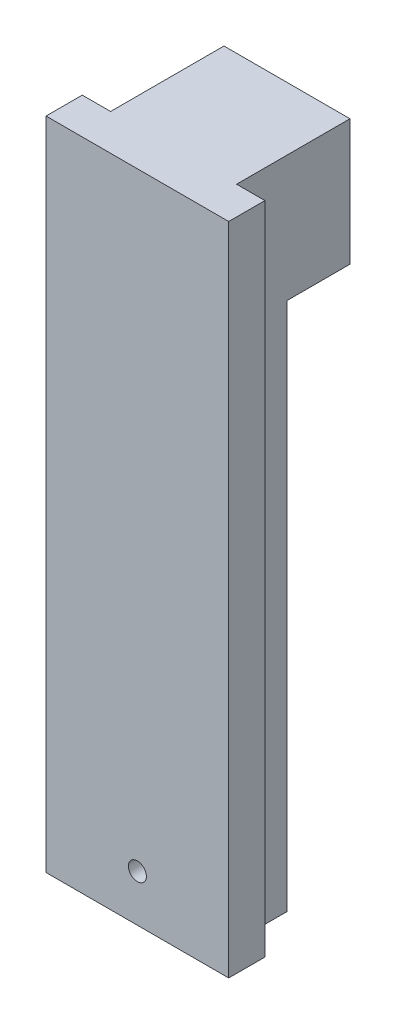
SolidWorks part; units mm, degrees
ref_plane "Płaszczyzna przednia" through (0, 0, 0) normal (0, 0, 1) x (1, 0, 0)
ref_plane "Płaszczyzna górna" through (0, 0, 0) normal (0, 1, 0) x (1, 0, 0)
ref_plane "Płaszczyzna prawa" through (0, 0, 0) normal (1, 0, 0) x (0, 0, -1)
sketch "Szkic1" plane through (0, 0, 0) normal (0, 1, 0) x (1, 0, 0)
  line L0 (0, -6) -> (0, 0) construction
  line L1 (0, 13.75) -> (0, 0) construction
  line L7 (-14.5, 0) -> (14.5, 0)
  line L8 (19, 5.75) -> (10, 5.75) construction
  line L10 (14.5, 0) -> (14.5, 5.75)
  line L11 (14.5, 5.75) -> (10, 5.75)
  line L12 (10, 5.75) -> (10, 13.75)
  line L13 (10, 13.75) -> (-10, 13.75)
  line L14 (-10, 13.75) -> (-10, 5.75)
  line L15 (-10, 5.75) -> (-14.5, 5.75)
  line L16 (-14.5, 5.75) -> (-14.5, 0)
  dimension "D1" = 6
  dimension "D4" = 9
  dimension "D5" = 29
  dimension "D6" = 20
  dimension "D7" = 5.75
  dimension "D8" = 4.5
  dimension "D9" = 29
  dimension "D10" = 20
  dimension "D11" = 20
  dimension "D12" = 8
extrude "Dodanie-wyciągnięcie1" add sketch "Szkic1" along normal blind 104
sketch "Szkic2" plane through (0, 0, -13.75) normal (0, 0, -1) x (-1, 0, 0)
  line L0 (-10, 104) -> (10, 104)
  line L1 (10, 104) -> (10, 84)
  line L2 (10, 104) -> (10, 0) construction
  line L3 (10, 84) -> (-10, 84)
  line L4 (-10, 104) -> (-10, 0) construction
  line L5 (-10, 84) -> (-10, 104)
  dimension "D1" = 20
extrude "Dodanie-wyciągnięcie2" add sketch "Szkic2" along normal blind 10
sketch "Szkic3" plane through (0, 0, -23.75) normal (0, 0, -1) x (-1, 0, 0)
  line L0 (-10, 94) -> (10, 94) construction
  line L1 (-10, 104) -> (-10, 84) construction
  line L2 (10, 84) -> (10, 104) construction
  line L3 (0, 104) -> (0, 84) construction
  line L4 (10, 104) -> (-10, 104) construction
  line L5 (-10, 84) -> (10, 84) construction
  circle A0 centre (0, 94) radius 2.5
  dimension "D1" = 5
extrude "Wytnij-wyciągnięcie1" cut sketch "Szkic3" against normal blind 10
sketch "Szkic4" plane through (0, 0, 0) normal (0, 0, 1) x (1, 0, 0)
  line L0 (0, 0) -> (0, 6) construction
  circle A0 centre (0, 7.425) radius 1.425
  dimension "D2" = 2.85
  dimension "D1" = 6
extrude "Wytnij-wyciągnięcie2" cut sketch "Szkic4" against normal through all
